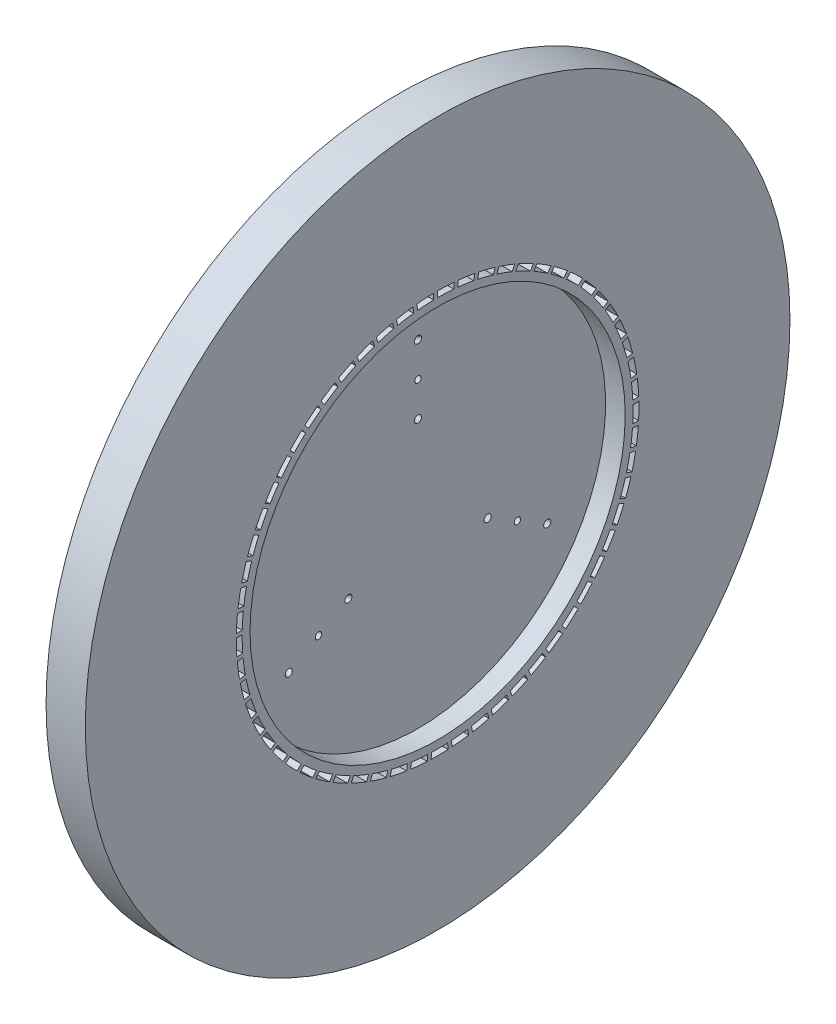
SolidWorks part; units mm, degrees
ref_plane "Front Plane" through (0, 0, 0) normal (0, 0, 1) x (1, 0, 0)
ref_plane "Top Plane" through (0, 0, 0) normal (0, 1, 0) x (1, 0, 0)
ref_plane "Right Plane" through (0, 0, 0) normal (1, 0, 0) x (0, 0, -1)
sketch "Sketch1" plane through (0, 0, 0) normal (1, 0, 0) x (0, 0, -1)
  circle A0 centre (0, 0) radius 89.825
  circle A5 centre (0, 0) radius 47.825
  dimension "D1" = 179.65
  dimension "D2" = 95.65
extrude "Flange" add sketch "Sketch1" along normal blind 10
sketch "Regen Slots Sketch" plane through (10, 0, 0) normal (1, 0, 0) x (0, 0, -1)
  line L0 (0, 49.825) -> (0, 51.325)
  line L1 (-1, 49.815) -> (-1, 51.3153)
  line L2 (5.1231, 49.5609) -> (5.2773, 51.053)
  line L3 (4.1273, 49.6538) -> (4.2816, 51.1461)
  line L4 (10.1918, 48.7715) -> (10.4986, 50.2398)
  line L5 (9.2109, 48.9662) -> (9.5178, 50.4348)
  line L6 (15.1525, 47.4651) -> (15.6087, 48.894)
  line L7 (14.1968, 47.7596) -> (14.6531, 49.1888)
  line L8 (19.9526, 45.6555) -> (20.5533, 47.03)
  line L9 (19.0323, 46.0467) -> (19.6331, 47.4215)
  line L10 (24.5412, 43.362) -> (25.28, 44.6674)
  line L11 (23.666, 43.8458) -> (24.4049, 45.1515)
  line L12 (28.8697, 40.6088) -> (29.7388, 41.8313)
  line L13 (28.0488, 41.18) -> (28.9181, 42.4028)
  line L14 (32.8921, 37.4251) -> (33.8823, 38.5518)
  line L15 (32.1343, 38.0778) -> (33.1247, 39.2047)
  line L16 (36.5658, 33.8448) -> (37.6667, 34.8637)
  line L17 (35.8792, 34.5719) -> (36.9802, 35.591)
  line L18 (39.852, 29.9057) -> (41.0517, 30.806)
  line L19 (39.2437, 30.6995) -> (40.4437, 31.6)
  line L20 (42.7157, 25.6496) -> (44.0017, 26.4217)
  line L21 (42.1923, 26.5017) -> (43.4785, 27.274)
  line L22 (45.1266, 21.1215) -> (46.4852, 21.7574)
  line L23 (44.6936, 22.023) -> (46.0524, 22.659)
  line L24 (47.0592, 16.3696) -> (48.4759, 16.8624)
  line L25 (46.7212, 17.3108) -> (48.1382, 17.8037)
  line L26 (48.4929, 11.4442) -> (49.9528, 11.7887)
  line L27 (48.2534, 12.4152) -> (49.7136, 12.7597)
  line L28 (49.4126, 6.3974) -> (50.9002, 6.59)
  line L29 (49.2742, 7.3879) -> (50.7621, 7.5805)
  line L30 (49.8085, 1.2829) -> (51.308, 1.3215)
  line L31 (49.7727, 2.2823) -> (51.2725, 2.3209)
  line L32 (49.6764, -3.8453) -> (51.1719, -3.961)
  line L33 (49.7436, -2.8475) -> (51.2394, -2.9633)
  line L34 (49.0177, -8.9327) -> (50.4934, -9.2016)
  line L35 (49.1871, -7.9471) -> (50.6631, -8.216)
  line L36 (47.8395, -13.9254) -> (49.2797, -14.3446)
  line L37 (48.1093, -12.9624) -> (49.5498, -13.3817)
  line L38 (46.1541, -18.7705) -> (47.5436, -19.3356)
  line L39 (46.5215, -17.8404) -> (47.9113, -18.4056)
  line L40 (43.9795, -23.4166) -> (45.3035, -24.1216)
  line L41 (44.4406, -22.5292) -> (45.7649, -23.2343)
  line L42 (41.3387, -27.8145) -> (42.5832, -28.6519)
  line L43 (41.8886, -26.9792) -> (43.1333, -27.8167)
  line L44 (38.2596, -31.9176) -> (39.4115, -32.8784)
  line L45 (38.8925, -31.1432) -> (40.0446, -32.1043)
  line L46 (34.7751, -35.6823) -> (35.822, -36.7565)
  line L47 (35.4842, -34.9772) -> (36.5313, -36.0516)
  line L48 (30.9219, -39.0688) -> (31.8528, -40.2449)
  line L49 (31.6998, -38.4403) -> (32.6309, -39.6167)
  line L50 (26.7409, -42.0411) -> (27.5459, -43.3068)
  line L51 (27.5793, -41.496) -> (28.3845, -42.7619)
  line L52 (22.2764, -44.5678) -> (22.9471, -45.9095)
  line L53 (23.1664, -44.1117) -> (23.8372, -45.4537)
  line L54 (17.5759, -46.6221) -> (18.105, -48.0257)
  line L55 (18.508, -46.2599) -> (19.0373, -47.6638)
  line L56 (12.689, -48.1822) -> (13.071, -49.6327)
  line L57 (13.6535, -47.9178) -> (14.0355, -49.3686)
  line L58 (7.6676, -49.2315) -> (7.8984, -50.7136)
  line L59 (8.6541, -49.0677) -> (8.885, -50.5501)
  line L60 (2.5649, -49.7589) -> (2.6421, -51.2569)
  line L61 (3.5631, -49.6974) -> (3.6403, -51.1957)
  line L62 (-2.5649, -49.7589) -> (-2.6421, -51.2569)
  line L63 (-1.5657, -49.8004) -> (-1.643, -51.2987)
  line L64 (-7.6676, -49.2315) -> (-7.8984, -50.7136)
  line L65 (-6.678, -49.3755) -> (-6.9088, -50.8579)
  line L66 (-12.689, -48.1822) -> (-13.071, -49.6327)
  line L67 (-11.7194, -48.4271) -> (-12.1015, -49.8779)
  line L68 (-17.5759, -46.6221) -> (-18.105, -48.0257)
  line L69 (-16.6366, -46.9655) -> (-17.1658, -48.3693)
  line L70 (-22.2764, -44.5678) -> (-22.9471, -45.9095)
  line L71 (-21.3775, -45.0059) -> (-22.0482, -46.3479)
  line L72 (-26.7409, -42.0411) -> (-27.5459, -43.3068)
  line L73 (-25.8917, -42.5693) -> (-26.6969, -43.8353)
  line L74 (-30.9219, -39.0688) -> (-31.8528, -40.2449)
  line L75 (-30.1315, -39.6815) -> (-31.0626, -40.8579)
  line L76 (-34.7751, -35.6823) -> (-35.822, -36.7565)
  line L77 (-34.0519, -36.373) -> (-35.099, -37.4475)
  line L78 (-38.2596, -31.9176) -> (-39.4115, -32.8784)
  line L79 (-37.6113, -32.679) -> (-38.7634, -33.6401)
  line L80 (-41.3387, -27.8145) -> (-42.5832, -28.6519)
  line L81 (-40.7721, -28.6386) -> (-42.0168, -29.4761)
  line L82 (-43.9795, -23.4166) -> (-45.3035, -24.1216)
  line L83 (-43.5006, -24.2946) -> (-44.8249, -24.9997)
  line L84 (-46.1541, -18.7705) -> (-47.5436, -19.3356)
  line L85 (-45.7681, -19.693) -> (-47.1578, -20.2582)
  line L86 (-47.8395, -13.9254) -> (-49.2797, -14.3446)
  line L87 (-47.5503, -14.8827) -> (-48.9909, -15.302)
  line L88 (-49.0177, -8.9327) -> (-50.4934, -9.2016)
  line L89 (-48.8286, -9.9147) -> (-50.3046, -10.1836)
  line L90 (-49.6764, -3.8453) -> (-51.1719, -3.961)
  line L91 (-49.5892, -4.8415) -> (-51.085, -4.9573)
  line L92 (-49.8085, 1.2829) -> (-51.308, 1.3215)
  line L93 (-49.8242, 0.283) -> (-51.324, 0.3216)
  line L94 (-49.4126, 6.3974) -> (-50.9002, 6.59)
  line L95 (-49.531, 5.4044) -> (-51.0189, 5.5971)
  line L96 (-48.4929, 11.4442) -> (-49.9528, 11.7887)
  line L97 (-48.7128, 10.4686) -> (-50.173, 10.8132)
  line L98 (-47.0592, 16.3696) -> (-48.4759, 16.8624)
  line L99 (-47.3782, 15.4218) -> (-48.7953, 15.9147)
  line L100 (-45.1266, 21.1215) -> (-46.4852, 21.7574)
  line L101 (-45.5414, 20.2116) -> (-46.9003, 20.8476)
  line L102 (-42.7157, 25.6496) -> (-44.0017, 26.4217)
  line L103 (-43.2219, 24.7871) -> (-44.5081, 25.5594)
  line L104 (-39.852, 29.9057) -> (-41.0517, 30.806)
  line L105 (-40.4442, 29.0998) -> (-41.6442, 30.0003)
  line L106 (-36.5658, 33.8448) -> (-37.6667, 34.8637)
  line L107 (-37.2377, 33.1041) -> (-38.3388, 34.1232)
  line L108 (-32.8921, 37.4251) -> (-33.8823, 38.5518)
  line L109 (-33.6366, 36.7575) -> (-34.627, 37.8844)
  line L110 (-28.8697, 40.6088) -> (-29.7388, 41.8313)
  line L111 (-29.6789, 40.0212) -> (-30.5482, 41.244)
  line L112 (-24.5412, 43.362) -> (-25.28, 44.6674)
  line L113 (-25.4065, 42.8607) -> (-26.1455, 44.1664)
  line L114 (-19.9526, 45.6555) -> (-20.5533, 47.03)
  line L115 (-20.8649, 45.2458) -> (-21.4657, 46.6206)
  line L116 (-15.1525, 47.4651) -> (-15.6087, 48.894)
  line L117 (-16.1021, 47.1514) -> (-16.5584, 48.5806)
  line L118 (-10.1918, 48.7715) -> (-10.4986, 50.2398)
  line L119 (-11.1686, 48.5571) -> (-11.4755, 50.0257)
  line L120 (-5.1231, 49.5609) -> (-5.2773, 51.053)
  line L121 (-6.1167, 49.4481) -> (-6.271, 50.9405)
  circle A0 centre (0, 0) radius 49.825
  circle A1 centre (0, 0) radius 51.325
  circle A2 centre (0, 0) radius 47.825 construction
  point P253 (0, 0)
  dimension "D2" = 1.5
  dimension "D3" = 2
  dimension "D4" = 61
extrude "Regen Slots" cut sketch "Regen Slots Sketch" against normal blind 25 contours L117 A1 L114 A0 | L119 A1 L116 A0 | L121 A1 L118 A0 | L1 A1 L120 A0 | L3 A1 L0 A0 | L5 A1 L2 A0 | L7 A1 L4 A0 | L9 A1 L6 A0 | L11 A1 L8 A0 | L13 A1 L10 A0 | L15 A1 L12 A0 | L17 A1 L14 A0 | L19 A1 L16 A0 | L21 A1 L18 A0 | L23 A1 L20 A0 | L25 A1 L22 A0 | L27 A1 L24 A0 | L29 A1 L26 A0 | L31 A1 L28 A0 | L33 A1 L30 A0 | L35 A1 L32 A0 | L37 A1 L34 A0 | L39 A1 L36 A0 | L41 A1 L38 A0 | L43 A1 L40 A0 | L45 A1 L42 A0 | L47 A1 L44 A0 | L49 A1 L46 A0 | L51 A1 L48 A0 | L53 A1 L50 A0 | L55 A1 L52 A0 | L57 A1 L54 A0 | L59 A1 L56 A0 | L61 A1 L58 A0 | L63 A1 L60 A0 | L65 A1 L62 A0 | L67 A1 L64 A0 | L69 A1 L66 A0 | L71 A1 L68 A0 | L73 A1 L70 A0 | L75 A1 L72 A0 | L77 A1 L74 A0 | L79 A1 L76 A0 | L81 A1 L78 A0 | L83 A1 L80 A0 | L85 A1 L82 A0 | L87 A1 L84 A0 | L89 A1 L86 A0 | L91 A1 L88 A0 | L93 A1 L90 A0 | L95 A1 L92 A0 | L97 A1 L94 A0 | L99 A1 L96 A0 | L101 A1 L98 A0 | L103 A1 L100 A0 | L107 A1 L104 A0 | L109 A1 L106 A0 | L111 A1 L108 A0 | L113 A1 L110 A0 | L115 A1 L112 A0 | L105 A1 L102 A0 region at (10, 50.5212, -2.1037) region at (10, 50.4697, 3.1021) region at (10, 50.0371, -7.2872) region at (10, 49.8833, 8.275) region at (10, 49.0227, -12.3934) region at (10, 48.7681, 13.3602) region at (10, 47.4885, -17.3683) region at (10, 47.1359, 18.3038) region at (10, 45.451, -22.1591) region at (10, 45.004, 23.0533) region at (10, 42.9317, -26.7149) region at (10, 42.3951, 27.5585) region at (10, 39.9573, -30.9876) region at (10, 39.3368, 31.7715) region at (10, 36.5593, -34.9318) region at (10, 35.8616, 35.6478) region at (10, 32.7739, -38.5057) region at (10, 32.0062, 39.1462) region at (10, 28.6409, -41.6715) region at (10, 27.8115, 42.2296) region at (10, 24.2044, -44.3955) region at (10, 23.322, 44.8654) region at (10, 19.5114, -46.649) region at (10, 18.5853, 47.0256) region at (10, 14.6115, -48.4079) region at (10, 13.6515, 48.6873) region at (10, 9.5567, -49.6537) region at (10, 8.5731, 49.8329) region at (10, 4.4006, -50.3731) region at (10, 3.4038, 50.4503) region at (10, -0.8022, -50.5586) region at (10, -1.8016, 50.5329) region at (10, -5.9964, -50.2082) region at (10, -6.9879, 50.0798) region at (10, -11.1271, -49.3255) region at (10, -12.1001, 49.0959) region at (10, -16.1398, -47.92) region at (10, -17.0841, 47.5915) region at (10, -20.9814, -46.0065) region at (10, -21.8869, 45.5827) region at (10, -25.6007, -43.6053) region at (10, -26.4578, 43.0907) region at (10, -29.9485, -40.7419) region at (10, -30.7482, 40.1419) region at (10, -33.9789, -37.4466) region at (10, -34.7126, 36.7675) region at (10, -37.6491, -33.7544) region at (10, -38.3091, 33.0035) region at (10, -40.9202, -29.7044) region at (10, -41.4995, 28.8896) region at (10, -43.7576, -25.3395) region at (10, -44.25, 24.4694) region at (10, -46.1311, -20.706) region at (10, -46.5315, 19.7899) region at (10, -48.0156, -15.853) region at (10, -48.3197, 14.9006) region at (10, -49.3912, -10.832) region at (10, -49.5957, 9.8534) region at (10, -50.2431, -5.6961) region at (10, -50.3459, 4.7017)
sketch "Faceplate Extrusion to Manifold Sketch" plane through (0, 0, 0) normal (-1, 0, 0) x (0, 0, 1)
  circle A0 centre (0, 0) radius 47.825
  dimension "D1" = 95.65
extrude "Faceplate Extrusion to Manifold" add sketch "Faceplate Extrusion to Manifold Sketch" against normal blind 5 separate body
sketch "Faceplate Extrusion to Chamber Sketch" plane through (0, 0, 0) normal (-1, 0, 0) x (0, 0, 1)
  circle A0 centre (0, 0) radius 47.825
  dimension "D1" = 95.65
extrude "Faceplate Extrusion to Chamber" add sketch "Faceplate Extrusion to Chamber Sketch" along normal blind 5
sketch "O-Ring Slot Sketch" plane through (-5, 0, 0) normal (-1, 0, 0) x (0, 0, 1)
  circle A0 centre (0, 0) radius 47.825
  circle A1 centre (0, 0) radius 44.825
  dimension "D1" = 95.65
  dimension "D2" = 3
extrude "O-Ring Slot" cut sketch "O-Ring Slot Sketch" against normal blind 6.5
sketch "Fuel Orifices Sketch" plane through (-5, 0, 0) normal (-1, 0, 0) x (0, 0, 1)
  circle A0 centre (0, 32.2826) radius 0.9146 construction
  circle A1 centre (0, 29.2826) radius 0.8262
  circle A2 centre (0, 26.2826) radius 0.9146 construction
  circle A3 centre (22.7614, -13.1413) radius 0.9146 construction
  circle A4 centre (25.3595, -14.6413) radius 0.8262
  circle A5 centre (27.9576, -16.1413) radius 0.9146 construction
  circle A6 centre (-22.7614, -13.1413) radius 0.9146 construction
  circle A7 centre (-25.3595, -14.6413) radius 0.8262
  circle A8 centre (-27.9576, -16.1413) radius 0.9146 construction
  point P22 (0, 0)
  dimension "D1" = 1.8292
  dimension "D2" = 1.6524
  dimension "D5" = 29.2826
  dimension "D3" = 3
  dimension "D4" = 3
  dimension "D6" = 3
extrude "Fuel Orifices" cut sketch "Fuel Orifices Sketch" against normal through all
ref_plane "Orifice Ref Plane 1" through (0, 0, 0) normal (0, 0.866, 0.5) x (1, 0, 0)
sketch "Ox1 Guide Curve" plane through (0, 0, 0) normal (0, 0.866, 0.5) x (1, 0, 0)
  line L0 (-5, -32.2826) -> (5, -38.0561)
  line L2 (5, -47.825) -> (5, 47.825) construction
  line L5 (-5, -29.2826) -> (5, -29.2826) construction
  line L6 (-5, -28.4564) -> (-5, -30.1088) construction
  line L7 (5, -30.1088) -> (5, -28.4564) construction
  point P2 (0, 0)
  point P3 (0, 0)
  dimension "D1" = 30
sketch "Ox1 Profile" plane through (-5, 0, 0) normal (-1, 0, 0) x (0, 0, 1)
  line L0 (56.2638, -32.4839) -> (-56.2638, 32.4839) construction
  circle A0 centre (27.9576, -16.1413) radius 0.9146
  point P2 (0, 0)
  dimension "D2" = 3
  dimension "D1" = 1.8292
sweep "Ox1 Orifice 1" cut profiles "Ox1 Profile" path "Ox1 Guide Curve"
pattern_circular "Revolve Ox Orifice 1" count 3 over 360 about axis through (5, 0, 0) along (-1, 0, 0) of "Ox1 Orifice 1"
sketch "Ox2 Profile" plane through (-5, 0, 0) normal (-1, 0, 0) x (0, 0, 1)
  line L0 (56.2638, -32.4839) -> (-56.2638, 32.4839) construction
  circle A0 centre (22.7614, -13.1413) radius 0.9146
  dimension "D2" = 3
  dimension "D1" = 1.8292
sketch "Ox2 Guide Curve" plane through (0, 0, 0) normal (0, 0.866, 0.5) x (1, 0, 0)
  line L0 (-5, -26.2826) -> (5, -20.5091)
  line L1 (-5, -25.368) -> (-5, -27.1972) construction
  line L2 (5, -47.825) -> (5, 47.825) construction
  line L3 (-5, -26.2826) -> (5, -26.2826) construction
  dimension "D1" = 30
sweep "Ox Orifice 2" cut profiles "Ox2 Profile" path "Ox2 Guide Curve"
pattern_circular "Revolve Ox Orifice 2" count 3 over 360 about axis through (5, 0, 0) along (-1, 0, 0) of "Ox Orifice 2"
equation "\"Flange_Dia\"= 179.65"
equation "\"D1@Sketch1\"=\"Flange_Dia\""
equation "\"Regen_Thickness\"= 1.5"
equation "\"Regen_To_Inner\"=2"
equation "\"Faceplate_Area\"=95.65"
equation "\"Regen_Rib_Thickness\"=1"
equation "\"D2@Sketch1\"=\"Faceplate_Area\""
equation "\"Flange_Thickness\"= 10"
equation "\"D1@Flange\" = \"Flange_Thickness\""
equation "\"D1@Regen Slots Sketch\" = \"Regen_Rib_Thickness\""
equation "\"D2@Regen Slots Sketch\" = \"Regen_Thickness\""
equation "\"D3@Regen Slots Sketch\" = \"Regen_To_Inner\""
equation "\"D1@Faceplate Extrusion to Manifold Sketch\" = \"Faceplate_Area\""
equation "\"D1@Faceplate Extrusion to Chamber Sketch\" = \"Faceplate_Area\""
equation "\"Faceplate_To_Chamber_Extrusion\"=5"
equation "\"D1@Faceplate Extrusion to Chamber\"=\"Faceplate_To_Chamber_Extrusion\""
equation "\"D1@O-Ring Slot Sketch\" = \"Faceplate_Area\""
equation "\"Injector_MCCN_O-Ring\"=3"
equation "\"D2@O-Ring Slot Sketch\" = \"Injector_MCCN_O-Ring\""
equation "\"D1@O-Ring Slot\" =  ( \"Faceplate_To_Chamber_Extrusion\" )  +  ( \"Injector_MCCN_O-Ring\" / 2 ) "
equation "\"Ox_Orifice\" = 1.829247371"
equation "\"D1@Fuel Orifices Sketch\" = \"Ox_Orifice\""
equation "\"Fuel_Orifice\"= 1.65242067"
equation "\"D2@Fuel Orifices Sketch\" = \"Fuel_Orifice\""
equation "\"OxFuel_Dist_Downstream\"= 3"
equation "\"Fuel_Dist_From_Center\"=29.2826"
equation "\"D5@Fuel Orifices Sketch\" = \"Fuel_Dist_From_Center\""
equation "\"D3@Fuel Orifices Sketch\" = \"OxFuel_Dist_Downstream\""
equation "\"D4@Fuel Orifices Sketch\" = \"OxFuel_Dist_Downstream\""
equation "\"D1@Ox1 Profile\" = \"Ox_Orifice\""
equation "\"D1@Ox2 Profile\" = \"Ox_Orifice\""
equation "\"OxFuel_HalfAngle\"=30"
equation "\"D1@Ox2 Guide Curve\" = \"OxFuel_HalfAngle\""
equation "\"D2@Ox1 Profile\" = \"OxFuel_Dist_Downstream\""
equation "\"D2@Ox2 Profile\"=\"OxFuel_Dist_Downstream\""
equation "\"D1@Ox1 Guide Curve\"=\"OxFuel_HalfAngle\""
equation "\"Thickness_FuelMan\"=5"
equation "\"D1@Faceplate Extrusion to Manifold\"=\"Thickness_FuelMan\""
